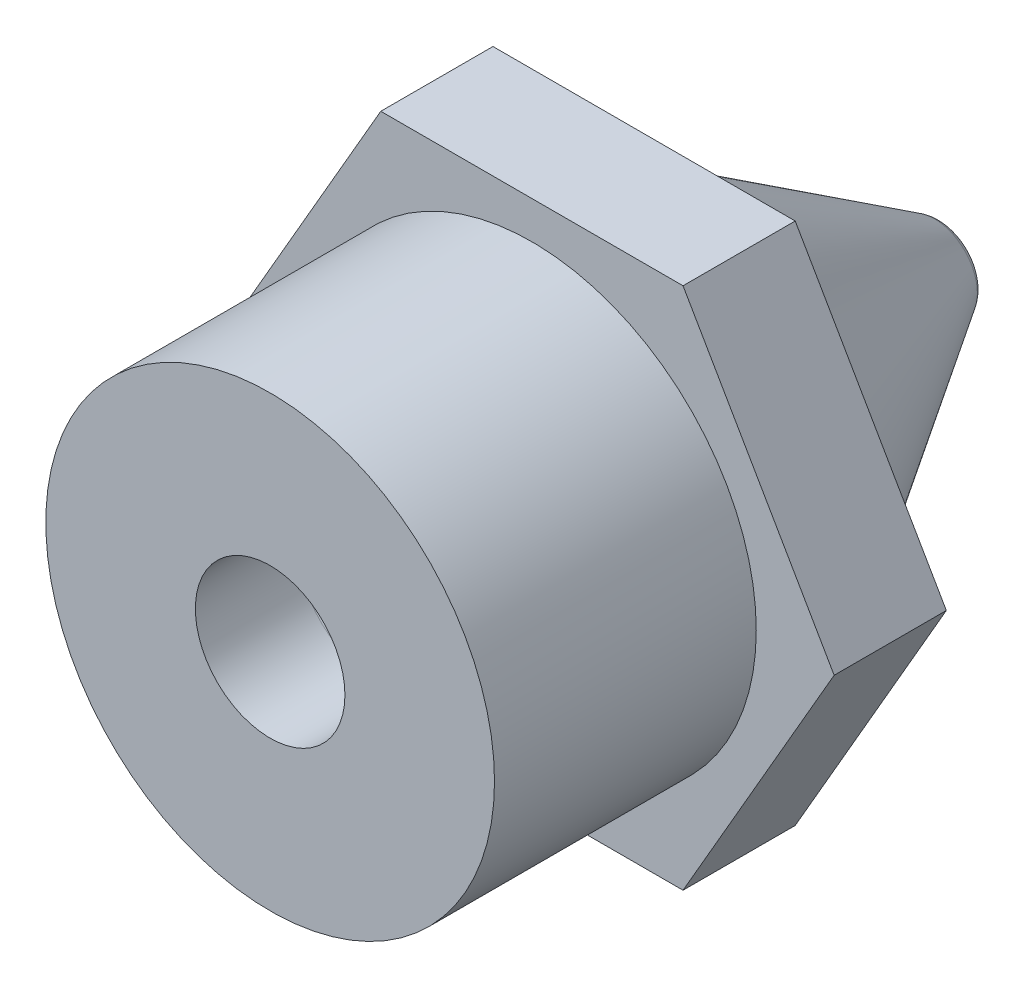
SolidWorks part; units mm, degrees
material "Laiton"
ref_plane "Plan de face" through (0, 0, 0) normal (0, 0, 1) x (1, 0, 0)
ref_plane "Plan de dessus" through (0, 0, 0) normal (0, 1, 0) x (1, 0, 0)
ref_plane "Plan de droite" through (0, 0, 0) normal (1, 0, 0) x (0, 0, -1)
sketch "Esquisse1" plane through (0, 0, 0) normal (0, 0, 1) x (1, 0, 0)
  line L1 (4.0415, 0) -> (2.0207, 3.5)
  line L2 (2.0207, 3.5) -> (-2.0207, 3.5)
  line L3 (-2.0207, 3.5) -> (-4.0415, 0)
  line L4 (-4.0415, 0) -> (-2.0207, -3.5)
  line L5 (-2.0207, -3.5) -> (2.0207, -3.5)
  line L6 (2.0207, -3.5) -> (4.0415, 0)
  circle A0 centre (0, 0) radius 3.5 construction
  dimension "D1" = 7
extrude "Boss.-Extru.1" add sketch "Esquisse1" along normal blind 9 contours L3 L4 L5 L6 L1 L2
sketch "Esquisse2" plane through (0, 0, 9) normal (0, 0, 1) x (1, 0, 0)
  line L1 (-9.4849, 6.2226) -> (10.1391, 6.2226)
  line L2 (-9.4849, 6.2226) -> (-9.4849, -9.3115)
  line L3 (-9.4849, -9.3115) -> (10.1391, -9.3115)
  line L4 (10.1391, 6.2226) -> (10.1391, -9.3115)
  circle A0 centre (0, 0) radius 3
  dimension "D1" = 6
extrude "Enlèv. mat.-Extru.1" cut sketch "Esquisse2" against normal blind 3.5
cosmetic thread "Représentation de filetage1" parameters "D1"=3.5, "D2"=4.891
sketch "Esquisse3" plane through (0, 0, 0) normal (0, 0, -1) x (-1, 0, 0)
  line L1 (5.6434, -6.9413) -> (-5.6238, -6.9413)
  line L2 (5.6434, -6.9413) -> (5.6434, 7.0198)
  line L3 (5.6434, 7.0198) -> (-5.6238, 7.0198)
  line L4 (-5.6238, -6.9413) -> (-5.6238, 7.0198)
  circle A0 centre (0, 0) radius 3
  dimension "D1" = 6
extrude "Enlèv. mat.-Extru.2" cut sketch "Esquisse3" against normal blind 4
chamfer "Chanfrein1" distance 4 angle 32 1 edges at (-3, 0, 0) first distance on face at (-3, 0, 4)
sketch "Esquisse4" plane through (0, 0, 0) normal (0, 1, 0) x (1, 0, 0)
  line L0 (0, -10.3816) -> (0, 2.1166) construction
  line L1 (0, -9) -> (1, -9)
  line L2 (-3, -9) -> (3, -9) construction
  line L3 (0, 0) -> (0.2, 0)
  line L4 (0.2, 0) -> (1, -7.6115)
  line L5 (0, -9) -> (0, 0)
  line L9 (1, -7.6115) -> (1, -9)
  dimension "D1" = 1
  dimension "D2" = 0.2
  dimension "D3" = 6
  dimension "D4" = 1.3885
revolve "Enlèvement de matière-Révolution1" cut sketch "Esquisse4" angle 360 about L0
fillet "Congé1" radius 0.25 1 edges at (0.5005, 0, 0)
